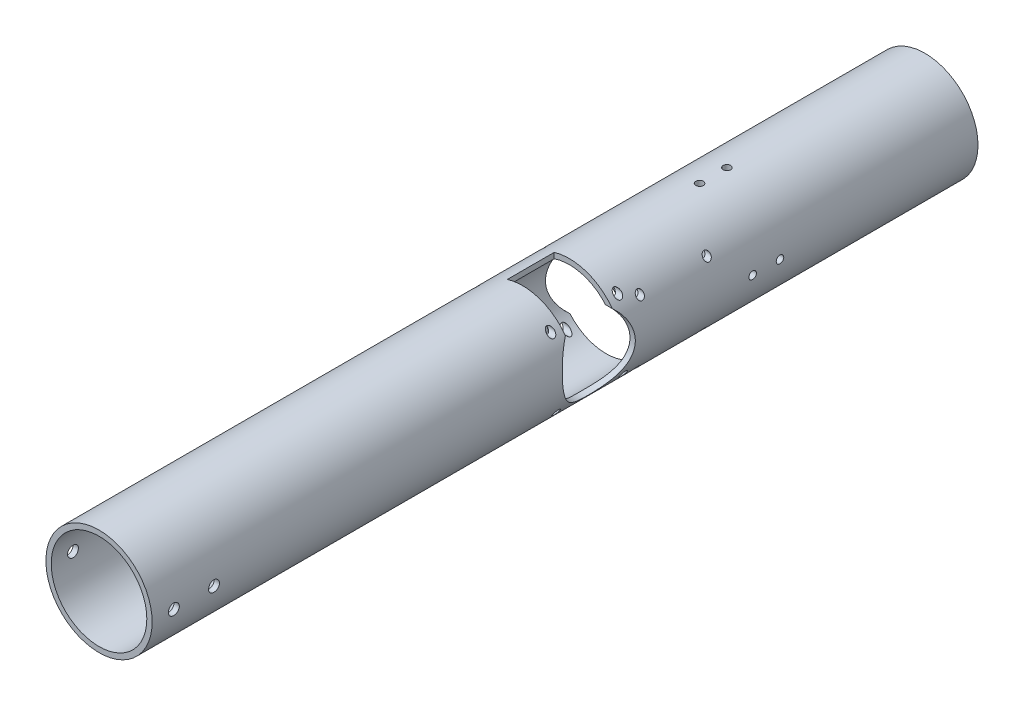
SolidWorks part; units mm, degrees
material "6061 Alloy"
ref_plane "Front Plane" through (0, 0, 0) normal (0, 0, 1) x (1, 0, 0)
ref_plane "Top Plane" through (0, 0, 0) normal (0, 1, 0) x (1, 0, 0)
ref_plane "Right Plane" through (0, 0, 0) normal (1, 0, 0) x (0, 0, -1)
sketch "Sketch1" plane through (0, 0, 0) normal (0, 0, 1) x (1, 0, 0)
  circle A0 centre (0, 0) radius 31.75
  circle A1 centre (0, 0) radius 28.575
  dimension "D1" = 63.5
  dimension "D2" = 57.15
extrude "Boss-Extrude1" add sketch "Sketch1" along normal blind 125 and the other way blind 250 contours A1 | A0
sketch "Sketch2" plane through (0, 0, 0) normal (1, 0, 0) x (0, 0, -1)
  circle A2 centre (73.488, -2) radius 21.75
  dimension "D1" = 43.5
  dimension "D2" = 73.488
  dimension "D3" = 2
extrude "Cut-Extrude1" cut sketch "Sketch2" against normal through all
sketch "Sketch3" plane through (0, 0, 0) normal (1, 0, 0) x (0, 0, -1)
  circle A1 centre (23.45, 2) radius 21.75
  dimension "D1" = 23.45
  dimension "D2" = 43.5
  dimension "D3" = 2
extrude "Cut-Extrude2" cut sketch "Sketch3" along normal through all
sketch "Sketch5" plane through (0, 0, 0) normal (1, 0, 0) x (0, 0, -1)
  line L1 (87.488, -12.75) -> (59.488, -12.75)
  line L2 (87.488, -12.75) -> (87.488, -34.75)
  line L3 (87.488, -34.75) -> (59.488, -34.75)
  line L4 (59.488, -12.75) -> (59.488, -34.75)
  line L5 (87.488, -12.75) -> (59.488, -34.75) construction
  line L6 (87.488, -34.75) -> (59.488, -12.75) construction
  circle A0 centre (73.488, -2) radius 21.75 construction
  circle A1 centre (73.488, -2) radius 21.75 construction
  circle A2 centre (73.488, -2) radius 21.75 construction
  point P0 (73.488, -23.75)
  dimension "D1" = 28
  dimension "D2" = 22
extrude "Cut-Extrude4" cut sketch "Sketch5" against normal through all from offset 9
sketch "Sketch6" plane through (0, 0, 0) normal (1, 0, 0) x (0, 0, -1)
  line L1 (9.45, 34.75) -> (37.45, 34.75)
  line L2 (9.45, 34.75) -> (9.45, 12.75)
  line L3 (9.45, 12.75) -> (37.45, 12.75)
  line L4 (37.45, 34.75) -> (37.45, 12.75)
  line L5 (9.45, 34.75) -> (37.45, 12.75) construction
  line L6 (9.45, 12.75) -> (37.45, 34.75) construction
  circle A0 centre (23.45, 2) radius 21.75 construction
  circle A1 centre (23.45, 2) radius 21.75 construction
  circle A2 centre (23.45, 2) radius 21.75 construction
  point P0 (23.45, 23.75)
  dimension "D1" = 28
  dimension "D2" = 22
extrude "Cut-Extrude5" cut sketch "Sketch6" along normal through all from offset 9 offset against normal yes
sketch "Sketch10" plane through (0, 0, 0) normal (1, 0, 0) x (0, 0, -1)
  line L1 (113.488, 38) -> (33.488, 38)
  line L2 (113.488, 38) -> (113.488, -42)
  line L3 (113.488, -42) -> (33.488, -42)
  line L4 (33.488, 38) -> (33.488, -42)
  line L5 (113.488, 38) -> (33.488, -42) construction
  line L6 (113.488, -42) -> (33.488, 38) construction
  point P0 (73.488, -2)
  dimension "D1" = 80
  dimension "D2" = 80
sketch "Sketch11" plane through (0, 0, 0) normal (1, 0, 0) x (0, 0, -1)
  line L0 (113.488, 38) -> (33.488, -42) construction
  line L1 (113.488, -42) -> (33.488, 38) construction
  line L2 (51.738, -2) -> (95.238, -2) construction
  line L3 (53.488, 18) -> (53.488, -22) construction
  circle A0 centre (93.488, 18) radius 2
  circle A1 centre (53.488, 18) radius 2
  circle A2 centre (53.488, -22) radius 2
  circle A3 centre (93.488, -22) radius 2
  arc A4 (87.488, -18.6452) -> (59.488, -18.6452) centre (73.488, -2) ccw construction
  arc A5 (87.488, -18.6452) -> (59.488, -18.6452) centre (73.488, -2) ccw construction
  point P18 (53.488, -2)
  dimension "D5" = 4
  dimension "D1" = 40
extrude "Cut-Extrude8" cut sketch "Sketch11" against normal through all both and the other way through all
sketch "Sketch12" plane through (0, 0, 0) normal (1, 0, 0) x (0, 0, -1)
  line L0 (-125, 31.75) -> (-125, -31.75) construction
  circle A0 centre (-112, 0) radius 3.25
  circle A1 centre (-88, 0) radius 3.25
  dimension "D2" = 6.5
  dimension "D3" = 24
  dimension "D4" = 13
extrude "Cut-Extrude10" cut sketch "Sketch12" against normal through all both and the other way through all
sketch "Sketch13" plane through (0, 0, 0) normal (0, 1, 0) x (1, 0, 0)
  line L0 (0, -34.925) -> (0, 34.925) construction
  line L1 (28.575, 250) -> (-28.575, 250) construction
  line L2 (0, 250) -> (0, -125) construction
  circle A0 centre (0, 238) radius 2.25 construction
  circle A1 centre (0, 205.9) radius 2.25 construction
  dimension "D2" = 4.5
  dimension "D3" = 32.1
  dimension "D1" = 12
sketch "Sketch14" plane through (0, 0, 0) normal (1, 0, 0) x (0, 0, -1)
  line L0 (3.45, -18) -> (3.45, 22) construction
  line L1 (-1.55, 27) -> (48.45, 27) construction
  line L2 (-1.55, 27) -> (-1.55, -23) construction
  line L3 (-1.55, -23) -> (48.45, -23) construction
  line L4 (48.45, 27) -> (48.45, -23) construction
  line L5 (-1.55, 27) -> (48.45, -23) construction
  line L6 (-1.55, -23) -> (48.45, 27) construction
  circle A0 centre (3.45, 22) radius 2
  circle A1 centre (43.45, 22) radius 2
  circle A2 centre (43.45, -18) radius 2
  circle A3 centre (3.45, -18) radius 2
  point P0 (23.45, 2)
  point P14 (3.45, 2)
  dimension "D5" = 4
  dimension "D1" = 40
  dimension "D2" = 50
sketch "Sketch15" plane through (0, 0, 0) normal (1, 0, 0) x (0, 0, -1)
  circle A0 centre (3.45, 22) radius 2
  circle A1 centre (43.45, 22) radius 2
  circle A2 centre (43.45, -18) radius 2
  circle A3 centre (3.45, -18) radius 2
  dimension "D1" = 4
extrude "Cut-Extrude12" cut sketch "Sketch15" against normal through all and the other way through all
hole_wizard "M4 Clearance Hole1" positions "Sketch18" profile "Sketch19" hole size "M4" standard "ANSI Metric"
sketch "Sketch18" plane through (0, 0, 0) normal (1, 0, 0) x (0, 0, -1)
  circle A0 centre (3.45, 22) radius 2 construction
  circle A1 centre (43.45, 22) radius 2 construction
  circle A2 centre (3.45, -18) radius 2 construction
  circle A3 centre (43.45, -18) radius 2 construction
  point P0 (3.45, 22)
  point P2 (43.45, 22)
  point P4 (3.45, -18)
  point P6 (43.45, -18)
  point P20 (93.488, 18)
  point P23 (53.488, 18)
  point P26 (93.488, -22)
  point P29 (53.488, -22)
sketch "Sketch19" plane through (0, 22, -3.45) normal (0, 1, 0) x (0, 0, 1)
  line L0 (0, 0) -> (0, 31.75)
  line L1 (0, 31.75) -> (2.25, 31.75)
  line L2 (2.25, 31.75) -> (2.25, 0)
  line L5 (2.25, 0) -> (0, 0)
  line L11 (0, -6.35) -> (0, 107.95) construction
  dimension "Thru Hole Dia." = 4.5
  dimension "Thru Hole Depth" = 31.75
mirror "Mirror1" about plane through (0, 0, 0) normal (1, 0, 0) of "M4 Clearance Hole1"
sketch "Sketch21" plane through (0, 0, -250) normal (0, 0, -1) x (-1, 0, 0)
  circle A0 centre (0, 0) radius 30
  dimension "D1" = 60
extrude "Cut-Extrude14" cut sketch "Sketch21" against normal blind 7
sketch "Sketch22" plane through (0, 0, 0) normal (1, 0, 0) x (0, 0, -1)
  line L0 (250, -31.75) -> (250, 31.75) construction
  line L1 (250, -31.75) -> (250, 31.75) construction
  circle A0 centre (221.65, 0) radius 2.25 construction
  circle A1 centre (131.65, 0) radius 2.25
  circle A2 centre (115.3, 0) radius 2.25
  circle A4 centre (238, 0) radius 2.25 construction
  point P14 (250, 0)
  dimension "D1" = 134.7
  dimension "D4" = 12
  dimension "D5" = 4.5
  dimension "D2" = 118.35
  dimension "D3" = 28.35
extrude "Cut-Extrude15" cut sketch "Sketch22" along normal through all
pattern_circular "CirPattern2" count 4 over 360 about axis through (0, 0, -250) along (0, 0, 1) of "Cut-Extrude15"
sketch "Sketch23" plane through (0, 0, -243) normal (0, 0, -1) x (-1, 0, 0)
  circle A0 centre (0, 0) radius 28.575 construction
  circle A1 centre (0, 0) radius 30
  circle A2 centre (0, 0) radius 30
  circle A3 centre (0, 0) radius 28.575
  dimension "D1" = 0
extrude "Boss-Extrude2" add sketch "Sketch23" along normal up to surface (7 mm away) up to face at (-30, 0, -250)
ref_plane "Plane1" through (0, 0, 75) normal (0, 0, 1) x (1, 0, 0)
split "Split1" trim tools "Plane1" bodies to split 124 resulting bodies 125 126
move or copy body "Body-Move/Copy1" bodies to move or copy 125 copy no translate (0, 0, 118.65) parameters "D1"=0, "D2"=0, "D3"=118.65
sketch "Sketch24" plane through (0, 0, 75) normal (0, 0, 1) x (1, 0, 0)
  circle A0 centre (0, 0) radius 28.575 construction
  circle A1 centre (0, 0) radius 31.75
  circle A2 centre (0, 0) radius 31.75
  circle A3 centre (0, 0) radius 28.575
  dimension "D1" = 0
extrude "Boss-Extrude3" add sketch "Sketch24" along normal up to surface (118.65 mm away) up to face at (31.75, 0, 193.65)
